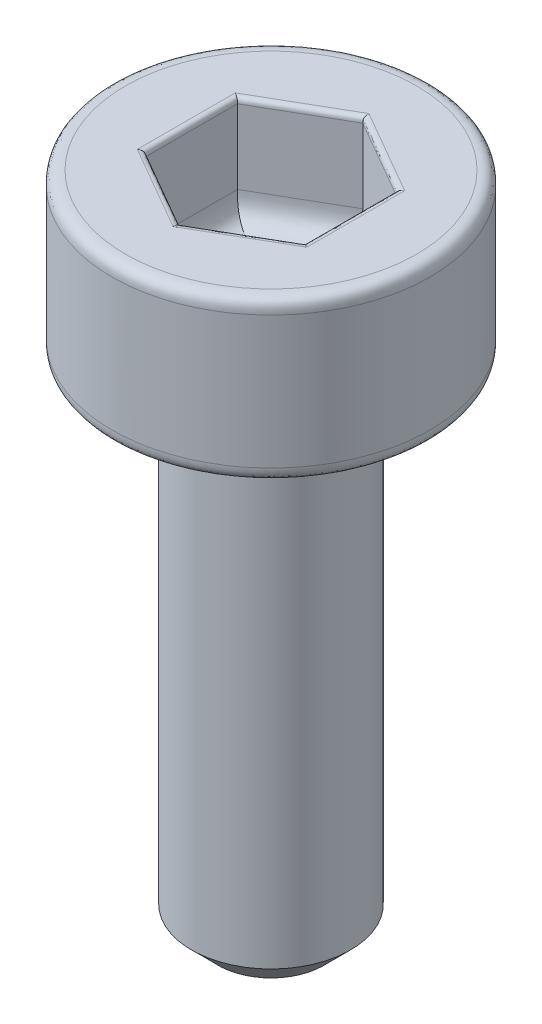
SolidWorks part; units mm, degrees
ref_plane "Front Plane" through (0, 0, 0) normal (0, 0, 1) x (1, 0, 0)
ref_plane "Top Plane" through (0, 0, 0) normal (0, 1, 0) x (1, 0, 0)
ref_plane "Right Plane" through (0, 0, 0) normal (1, 0, 0) x (0, 0, -1)
sketch "Sketch2" plane through (0, 0, 0) normal (1, 0, 0) x (0, 0, -1)
  line L0 (0, 0) -> (0, 25)
  line L1 (0, 25) -> (6, 25)
  line L2 (6, 25) -> (6, 19)
  line L3 (6, 19) -> (3, 19)
  line L4 (3, 19) -> (3, 0)
  line L5 (3, 0) -> (0, 0)
  dimension "D1" = 3
  dimension "D2" = 6
  dimension "D3" = 6
  dimension "D4" = 25
revolve "Revolve1" add sketch "Sketch2" angle 360 about L0
chamfer "Chamfer1" distance 1 angle 45 1 edges at (0, 0, -3)
sketch "Sketch3" plane through (0, 25, 0) normal (0, 1, 0) x (1, 0, 0)
  line L1 (0, 3.4641) -> (-3, 1.7321)
  line L2 (-3, 1.7321) -> (-3, -1.7321)
  line L3 (-3, -1.7321) -> (0, -3.4641)
  line L4 (0, -3.4641) -> (3, -1.7321)
  line L5 (3, -1.7321) -> (3, 1.7321)
  line L6 (3, 1.7321) -> (0, 3.4641)
  circle A0 centre (0, 0) radius 3 construction
  dimension "D1" = 6
extrude "Cut-Extrude1" cut sketch "Sketch3" against normal blind 4
fillet "Fillet1" radius 1 6 edges at (3, 21, 0) (1.5, 21, 2.5981) (-1.5, 21, 2.5981) (-3, 21, 0) (-1.5, 21, -2.5981) (1.5, 21, -2.5981) curvature continuous yes
fillet "Fillet2" radius 0.5 2 edges at (0, 19, -6) (0, 25, -6) curvature continuous yes
ref_axis "Axis1" through (0, 36, 0) along (0, -1, 0)
fillet "Fillet3" radius 0.2 6 edges at (-3, 25, 0) (-1.5, 25, 2.5981) (1.5, 25, 2.5981) (3, 25, 0) (1.5, 25, -2.5981) (-1.5, 25, -2.5981) curvature continuous yes
